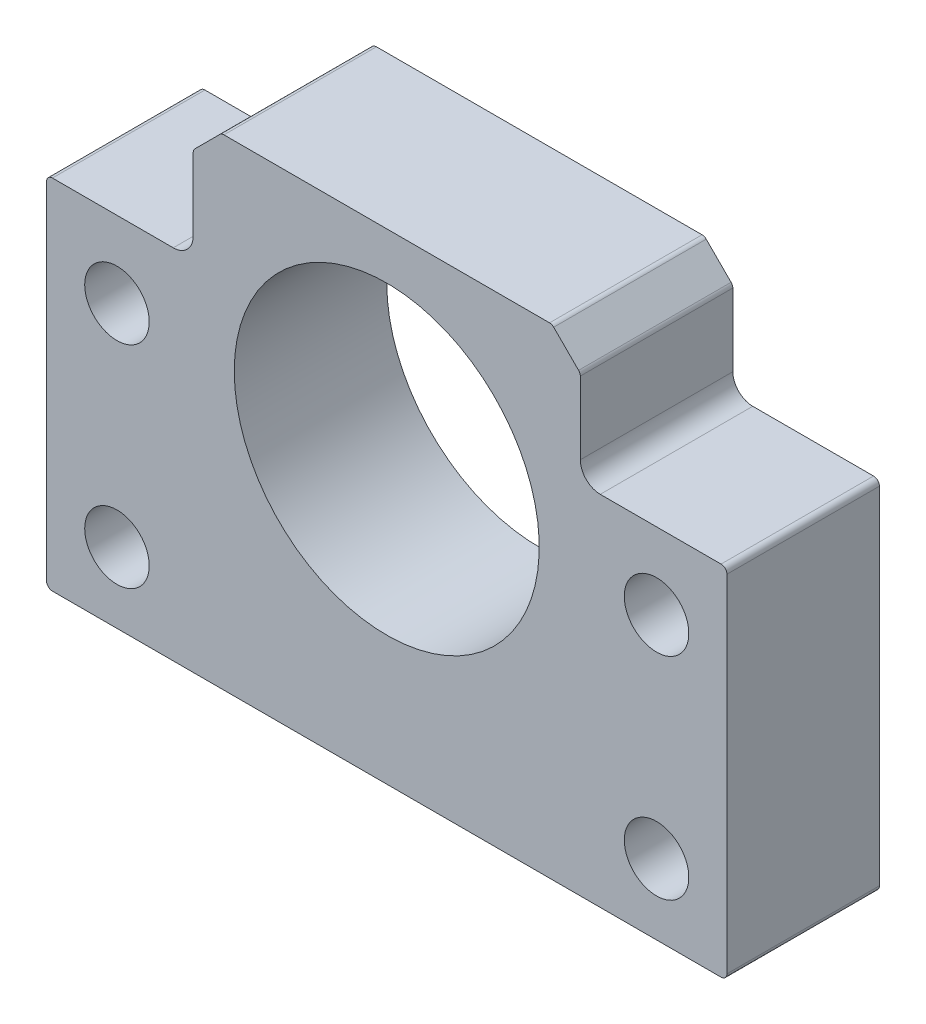
SolidWorks part; units mm, degrees
ref_plane "Front Plane" through (0, 0, 0) normal (0, 0, 1) x (1, 0, 0)
ref_plane "Top Plane" through (0, 0, 0) normal (0, 1, 0) x (1, 0, 0)
ref_plane "Right Plane" through (0, 0, 0) normal (1, 0, 0) x (0, 0, -1)
sketch "Sketch1" plane through (0, 0, 0) normal (0, 0, 1) x (1, 0, 0)
  line L20 (40.028, 14.697) -> (27.528, 14.697)
  line L21 (27.528, 14.697) -> (27.528, 22.7828)
  line L22 (27.528, 22.7828) -> (25.1138, 25.197)
  line L23 (25.1138, 25.197) -> (-3.0578, 25.197)
  line L24 (-3.0578, 25.197) -> (-5.472, 22.7828)
  line L25 (-5.472, 22.7828) -> (-5.472, 14.697)
  line L26 (-5.472, 14.697) -> (-17.972, 14.697)
  line L27 (-17.972, 14.697) -> (-17.972, -15.803)
  line L28 (-17.972, -15.803) -> (40.028, -15.803)
  line L29 (40.028, -15.803) -> (40.028, 14.697)
  circle A6 centre (34.028, 8.197) radius 2.75
  circle A7 centre (34.028, -9.803) radius 2.75
  circle A8 centre (-11.972, -9.803) radius 2.75
  circle A9 centre (-11.972, 8.197) radius 2.75
  circle A11 centre (11.028, 8.197) radius 13
  point P12 (0, 0)
  point P15 (0, 0)
  dimension "D1" = 26
  dimension "D2" = 58
  dimension "D3" = 30.5
  dimension "D4" = 30.5
  dimension "D5" = 28.1716
  dimension "D6" = 8.0858
  dimension "D7" = 12.5
  dimension "D9" = 135
  dimension "D10" = 225
  dimension "D11" = 8.0858
  dimension "D12" = 41
  dimension "D13" = 3.4142
  dimension "D14" = 3.4142
extrude "Boss-Extrude1" add sketch "Sketch1" along normal blind 13
fillet "Fillet1" radius 1.7 2 edges at (27.528, 14.697, 6.5) (-5.472, 14.697, 6.5)
fillet "Fillet2" radius 0.5 8 edges at (-17.972, 14.697, 6.5) (-17.972, -15.803, 6.5) (40.028, -15.803, 6.5) (40.028, 14.697, 6.5) (27.528, 22.7828, 6.5) (25.1138, 25.197, 6.5) (-3.0578, 25.197, 6.5) (-5.472, 22.7828, 6.5)
sketch "Sketch2" plane through (0, 0, 0) normal (0, 0, -1) x (-1, 0, 0)
  line L0 (-8.5942, -15.803) -> (17.472, -15.803)
  line L3 (-12.885, 25.197) -> (-24.9066, 25.197)
  line L4 (-40.028, -4.0931) -> (-40.028, -15.303)
  line L7 (17.972, 0.9069) -> (17.972, 14.197)
  line L8 (17.972, 14.197) -> (17.972, -15.303) construction
  line L10 (17.972, -15.303) -> (17.972, 14.197)
  line L11 (17.472, 14.697) -> (7.172, 14.697)
  line L12 (5.472, 16.397) -> (5.472, 22.5757)
  line L13 (5.3256, 22.9292) -> (3.2043, 25.0505)
  line L14 (2.8507, 25.197) -> (-24.9066, 25.197)
  line L15 (-25.2602, 25.0505) -> (-27.3815, 22.9292)
  line L16 (-27.528, 22.5757) -> (-27.528, 16.397)
  line L17 (-29.228, 14.697) -> (-39.528, 14.697)
  line L18 (-40.028, 14.197) -> (-40.028, -15.303)
  line L19 (-39.528, -15.803) -> (17.472, -15.803)
  line L20 (17.972, -15.303) -> (17.972, -4.0931)
  line L21 (17.472, 14.697) -> (7.172, 14.697)
  line L22 (5.472, 16.397) -> (5.472, 22.5757)
  line L23 (5.3256, 22.9292) -> (3.2043, 25.0505)
  line L24 (2.8507, 25.197) -> (-7.885, 25.197)
  line L25 (-25.2602, 25.0505) -> (-27.3815, 22.9292)
  line L26 (-27.528, 22.5757) -> (-27.528, 16.397)
  line L27 (-29.228, 14.697) -> (-39.528, 14.697)
  line L28 (-40.028, 14.197) -> (-40.028, 0.9069)
  line L29 (-39.528, -15.803) -> (-13.5942, -15.803)
  arc A10 (17.972, 14.197) -> (17.472, 14.697) centre (17.472, 14.197) ccw
  arc A11 (5.472, 16.397) -> (7.172, 14.697) centre (7.172, 16.397) ccw
  arc A12 (5.472, 22.5757) -> (5.3256, 22.9292) centre (4.972, 22.5757) ccw
  arc A13 (3.2043, 25.0505) -> (2.8507, 25.197) centre (2.8507, 24.697) ccw
  arc A14 (-24.9066, 25.197) -> (-25.2602, 25.0505) centre (-24.9066, 24.697) ccw
  arc A15 (-27.3815, 22.9292) -> (-27.528, 22.5757) centre (-27.028, 22.5757) ccw
  arc A16 (-29.228, 14.697) -> (-27.528, 16.397) centre (-29.228, 16.397) ccw
  arc A17 (-39.528, 14.697) -> (-40.028, 14.197) centre (-39.528, 14.197) ccw
  arc A18 (-40.028, -15.303) -> (-39.528, -15.803) centre (-39.528, -15.303) ccw
  arc A19 (17.472, -15.803) -> (17.972, -15.303) centre (17.472, -15.303) ccw
  arc A20 (17.972, 14.197) -> (17.472, 14.697) centre (17.472, 14.197) ccw
  arc A21 (5.472, 16.397) -> (7.172, 14.697) centre (7.172, 16.397) ccw
  arc A22 (5.472, 22.5757) -> (5.3256, 22.9292) centre (4.972, 22.5757) ccw
  arc A23 (3.2043, 25.0505) -> (2.8507, 25.197) centre (2.8507, 24.697) ccw
  arc A24 (-24.9066, 25.197) -> (-25.2602, 25.0505) centre (-24.9066, 24.697) ccw
  arc A25 (-27.3815, 22.9292) -> (-27.528, 22.5757) centre (-27.028, 22.5757) ccw
  arc A26 (-29.228, 14.697) -> (-27.528, 16.397) centre (-29.228, 16.397) ccw
  arc A27 (-39.528, 14.697) -> (-40.028, 14.197) centre (-39.528, 14.197) ccw
  arc A28 (-40.028, -15.303) -> (-39.528, -15.803) centre (-39.528, -15.303) ccw
  arc A29 (17.472, -15.803) -> (17.972, -15.303) centre (17.472, -15.303) ccw
  point P9 (-67.8468, -37.3655)
  point P12 (22.7515, -36.6563)
  point P22 (30.7299, -35.1493)
  point P49 (-13.5942, -15.803)
  point P50 (17.972, -4.0931)
  point P53 (-40.028, -4.0931)
  point P54 (-3.0167, 18.4351)
  point P55 (-13.5942, -4.5701)
  point P56 (-23.5843, 6.5759)
  dimension "D2" = 5
  dimension "D3" = 5
  dimension "D4" = 5
  dimension "D5" = 5
  dimension "D1" = 0
sketch "Sketch3" plane through (0, 0, 0) normal (0, 0, -1) x (-1, 0, 0)
  arc A2 (-21.8167, 0.9441) -> (-0.2393, 0.9441) centre (-11.028, 8.197) ccw
  arc A4 (1.7002, 5.5526) -> (-8.5526, 20.9591) centre (-11.028, 8.197) ccw
  arc A5 (-13.5526, 20.9495) -> (-23.7562, 5.5526) centre (-11.028, 8.197) ccw
  circle A7 centre (-11.028, 8.197) radius 13 construction
  point P1 (-23.7562, 5.5526)
  point P3 (-57.623, 0)
  point P9 (0, 0)
  point P10 (0, 0)
  point P13 (1.7002, 5.5526)
  point P14 (-8.5526, 20.9591)
  dimension "D1" = 5
  dimension "D2" = 5
  dimension "D3" = 5
